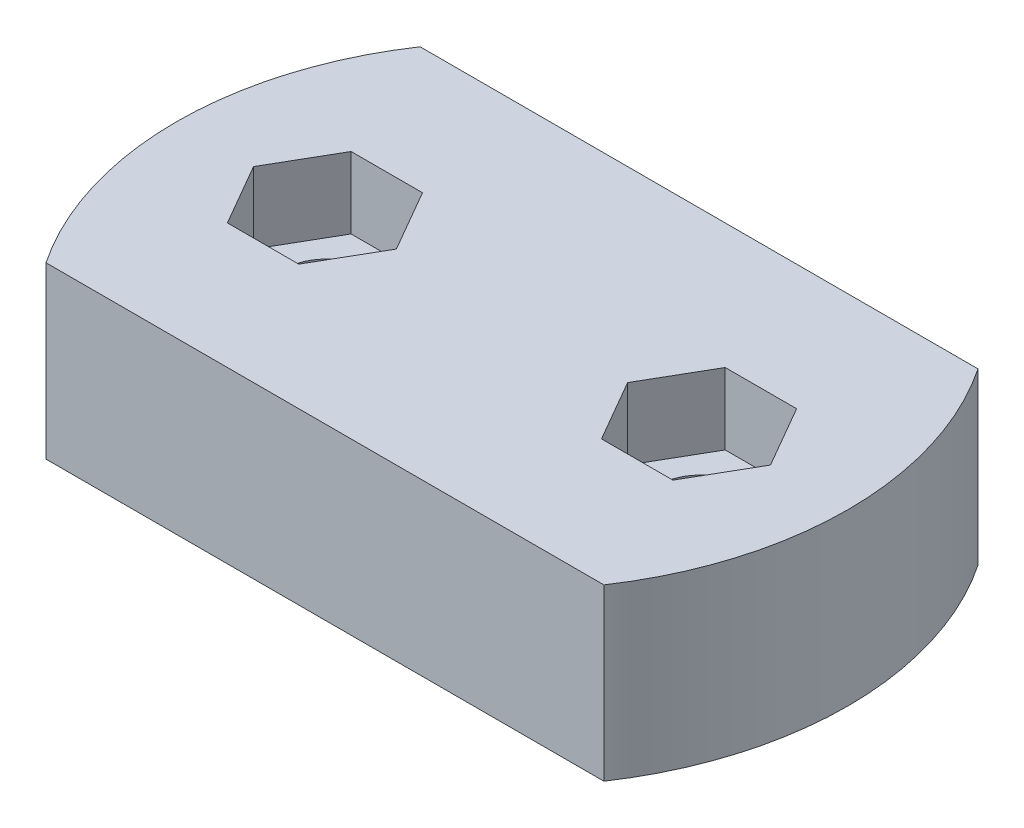
SolidWorks part; units mm, degrees
ref_plane "Front Plane" through (0, 0, 0) normal (0, 0, 1) x (1, 0, 0)
ref_plane "Top Plane" through (0, 0, 0) normal (0, 1, 0) x (1, 0, 0)
ref_plane "Right Plane" through (0, 0, 0) normal (1, 0, 0) x (0, 0, -1)
sketch "Sketch1" plane through (0, 0, 0) normal (0, 1, 0) x (1, 0, 0)
  circle A3 centre (0, 0) radius 19.75
  dimension "D1" = 39.5
extrude "Boss-Extrude1" add sketch "Sketch1" along normal mid plane 10 contours A3
sketch "Sketch2" plane through (0, 5, 0) normal (0, 1, 0) x (1, 0, 0)
  line L0 (0, 19.75) -> (0, -19.75) construction
  line L1 (-8.9, -3.6373) -> (-6.8, 0)
  line L2 (-6.8, 0) -> (-8.9, 3.6373)
  line L3 (-8.9, 3.6373) -> (-13.1, 3.6373)
  line L4 (-13.1, 3.6373) -> (-15.2, 0)
  line L5 (-15.2, 0) -> (-13.1, -3.6373)
  line L6 (-13.1, -3.6373) -> (-8.9, -3.6373)
  line L7 (-19.75, 0) -> (19.75, 0) construction
  line L8 (13.1, -3.6373) -> (8.9, -3.6373)
  line L9 (15.2, 0) -> (13.1, -3.6373)
  line L10 (13.1, 3.6373) -> (15.2, 0)
  line L11 (8.9, 3.6373) -> (13.1, 3.6373)
  line L12 (6.8, 0) -> (8.9, 3.6373)
  line L13 (8.9, -3.6373) -> (6.8, 0)
  circle A0 centre (-11, 0) radius 3.6373 construction
  circle A1 centre (0, 0) radius 19.75 construction
  point P15 (0, 0)
  dimension "D1" = 11
  dimension "D2" = 8.4
extrude "Cut-Extrude1" cut sketch "Sketch2" against normal blind 4.2
sketch "Sketch3" plane through (0, 0.8, 0) normal (0, 1, 0) x (1, 0, 0)
  line L0 (-11, 3.6373) -> (-11, -3.6373) construction
  line L1 (-8.9, 3.6373) -> (-13.1, 3.6373) construction
  line L2 (-13.1, -3.6373) -> (-8.9, -3.6373) construction
  line L3 (-6.8, 0) -> (-15.2, 0) construction
  line L4 (0, 19.75) -> (0, -19.75) construction
  circle A0 centre (0, 0) radius 19.75 construction
  point P0 (-11, 0)
  point P1 (11, 0)
  point P13 (-11, 0)
  point P15 (0, 0)
  point P19 (0, 0)
  point P20 (0, 0)
hole_wizard "#8 Clearance Hole1" positions "Sketch4" profile "Sketch5" hole size "#8" standard "ANSI Inch" end condition through all
sketch "Sketch4" plane through (0, 0.8, 0) normal (0, 1, 0) x (1, 0, 0)
  point P0 (-11, 0)
  point P3 (11, 0)
sketch "Sketch5" plane through (-11, 0.8, 0) normal (1, 0, 0) x (0, 0, 1)
  line L0 (0, 0) -> (0, 5.8)
  line L1 (0, 5.8) -> (2.2479, 5.8)
  line L2 (2.2479, 5.8) -> (2.2479, 0)
  line L5 (2.2479, 0) -> (0, 0)
  line L11 (0, -6.35) -> (0, 107.95) construction
  dimension "Thru Hole Dia." = 4.4958
  dimension "Thru Hole Depth" = 5.8
sketch "Sketch6" plane through (0, 5, 0) normal (0, 1, 0) x (1, 0, 0)
  line L0 (-16.4031, 11) -> (16.4031, 11)
  line L1 (-16.4031, -11) -> (16.4031, -11)
  arc A0 (-16.4031, 11) -> (-16.4031, -11) centre (0, 0) ccw
  circle A1 centre (0, 0) radius 19.75 construction
  arc A2 (16.4031, -11) -> (16.4031, 11) centre (0, 0) ccw
  circle M17 centre (0, 0) radius 19.75
  dimension "D1" = 11
  dimension "D2" = 11
extrude "Cut-Extrude2" cut sketch "Sketch6" against normal blind 10 contours L0 M17 | L1 M17 region at (0, 5, -14.5763) region at (0, 5, 14.5763)
